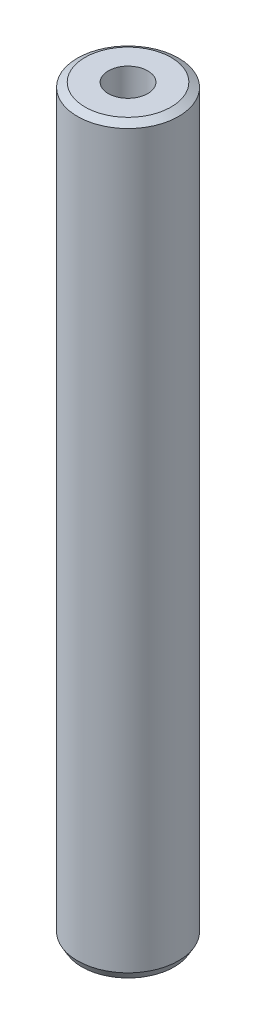
SolidWorks part; units mm, degrees
ref_plane "Front Plane" through (0, 0, 0) normal (0, 0, 1) x (1, 0, 0)
ref_plane "Top Plane" through (0, 0, 0) normal (0, 1, 0) x (1, 0, 0)
ref_plane "Right Plane" through (0, 0, 0) normal (1, 0, 0) x (0, 0, -1)
sketch "Sketch1" plane through (0, 0, 0) normal (0, 1, 0) x (1, 0, 0)
  circle A0 centre (0, 0) radius 37.5
  dimension "SHAFT_OD" = 75
extrude "Boss-Extrude1" add sketch "Sketch1" along normal blind 550.9289
sketch "Sketch2" plane through (0, 0, 0) normal (0, 1, 0) x (1, 0, 0)
  circle A0 centre (0, 0) radius 14.6398
  dimension "BORE_D" = 29.2796
extrude "Cut-Extrude1" cut sketch "Sketch2" along normal through all
chamfer "Chamfer1" distance 3.2362 angle 60 2 edges at (0, 550.9289, 37.5) (0, 0, 37.5) first distance on face at (0, 550.9289, 37.5) first distance on face at (0, 0, 14.6398)
